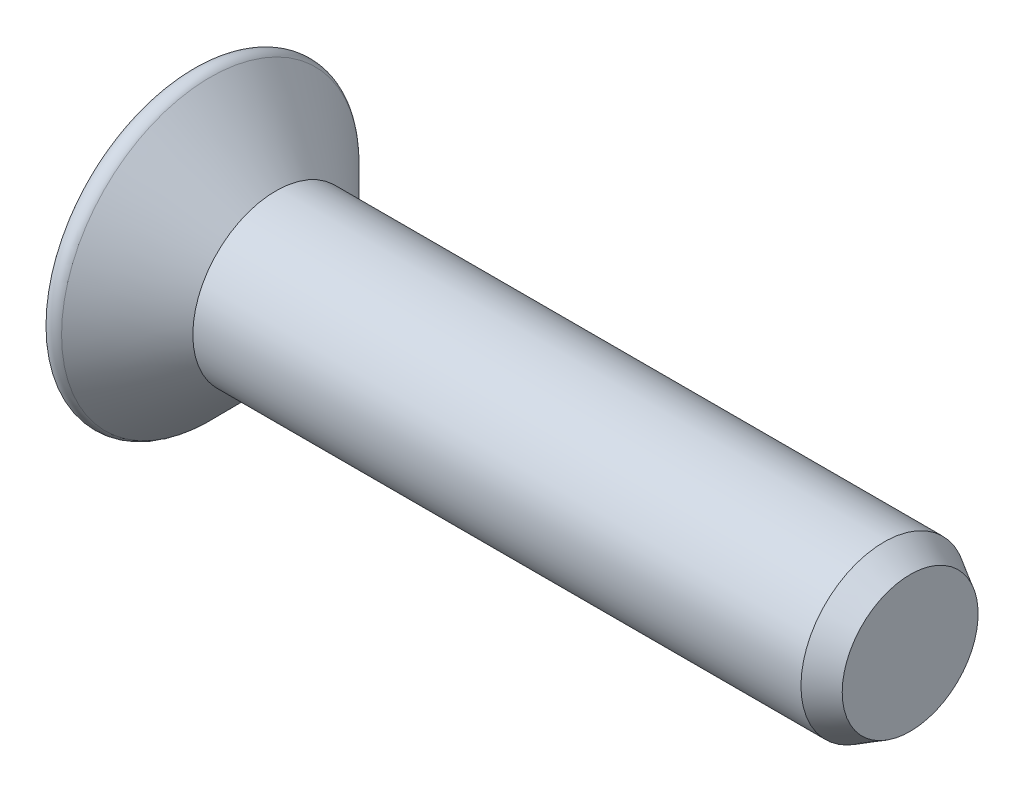
SolidWorks part; units mm, degrees
ref_plane "Front Plane" through (0, 0, 0) normal (0, 0, 1) x (1, 0, 0)
ref_plane "Top Plane" through (0, 0, 0) normal (0, 1, 0) x (1, 0, 0)
ref_plane "Right Plane" through (0, 0, 0) normal (1, 0, 0) x (0, 0, -1)
sketch "Sketch1" plane through (0, 0, 0) normal (0, 0, 1) x (1, 0, 0)
  line L0 (0, 0) -> (6.2784, 0) construction
  line L3 (-1.6, 0) -> (-1.6, -1.8061) construction
  line L4 (-1.6, 0) -> (8.4, 0)
  line L5 (0, 1.1) -> (8.4, 1.1)
  line L6 (8.4, 1.1) -> (8.4, 0)
  line L7 (0, 1.1) -> (-0.869, 1.969)
  arc A0 (-1.1, 1.9365) -> (-1.6, 0) centre (2.4, 0) ccw
  arc A1 (-1.1, 1.9365) -> (-0.869, 1.969) centre (-0.9723, 1.8658) cw
  dimension "D1" = 45
  dimension "l" = 9.5
revolve "Revolve1" add sketch "Sketch1" angle 360 about L0
cosmetic thread "ThreadCosmetic" [suppressed] parameters "D1"=9.3, "D2"=1.65
chamfer "Chamfer1" distance 0.2 angle 60 1 edges at (8.4, 0, 1.1) first distance on face at (8.4, 0, 1.1)
sketch "Sketch5" plane through (0, 0, 0) normal (0, 0, 1) x (1, 0, 0)
  line L0 (0.3703, 0.825) -> (0.2069, 0.825)
  line L1 (0.2069, 0.825) -> (0.0481, 1.1)
  line L2 (0.3703, 0.825) -> (0.529, 1.1)
  line L3 (0.0481, 1.1) -> (0.0481, 1.35)
  line L4 (0.529, 1.1) -> (0.529, 1.35)
  line L5 (0.0481, 1.35) -> (0.529, 1.35)
  line L6 (0.2886, 0.825) -> (0.2886, 0) construction
  line L7 (0, 0) -> (7.3035, 0) construction
  line L9 (0, 1.1) -> (0, -1.1) construction
  line L12 (8.0536, 1.1) -> (0, 1.1) construction
  dimension "D2" = 60
  dimension "D3" = 0.25
  dimension "minordia" = 1.65
  dimension "threadstart" = 0.2886
revolve "ThreadSchematic" [suppressed] cut sketch "Sketch5" angle 360 about L7
pattern_linear "ThdSchPat" [suppressed] count 18 spacing 0.4809 along (1, 0, 0) of bodies 105
sketch "Sketch2" plane through (0, 0, 0) normal (0, 0, 1) x (1, 0, 0)
  line L0 (0, 0) -> (5.7679, 0) construction
  line L1 (8.4, 0) -> (6.4947, 1.1)
  line L2 (8.4, 1.1) -> (8.4, 0) construction
  line L4 (6.4947, 1.1) -> (6.4947, 1.2)
  line L5 (6.4947, 1.2) -> (8.5, 1.2)
  line L6 (8.5, 1.2) -> (8.5, 0)
  line L7 (8.5, 0) -> (8.4, 0)
  point P5 (0, 1.1)
  dimension "D1" = 30
  dimension "D2" = 0.1
  dimension "D3" = 0.1
revolve "EndCone" [suppressed] cut sketch "Sketch2" angle 360 about L0
ref_plane "Plane4" through (-1.6, 0, 0) normal (1, 0, 0) x (0, 0, -1)
sketch "Sketch3" plane through (-1.6, 0, 0) normal (1, 0, 0) x (0, 0, -1)
  line L0 (0, 2.343) -> (0, -2.4842) construction
  line L1 (2.7661, 0) -> (-3.4558, 0) construction
  line L2 (-0.22, 1.1) -> (0.22, 1.1)
  line L3 (0.22, 1.1) -> (0.1467, 0.7333)
  line L4 (0, 0) -> (1.9578, 1.9578) construction
  line L5 (0.1467, 0.7333) -> (0.3614, 0.3614)
  line L6 (0.1467, 0.7333) -> (0, 0) construction
  line L7 (-0.1467, 0.7333) -> (-0.3614, 0.3614)
  line L8 (-0.22, 1.1) -> (-0.1467, 0.7333)
  line L9 (1.1, 0.22) -> (1.1, -0.22)
  line L10 (1.1, -0.22) -> (0.7333, -0.1467)
  line L11 (0.7333, -0.1467) -> (0.3614, -0.3614)
  line L12 (0.7333, 0.1467) -> (0.3614, 0.3614)
  line L13 (1.1, 0.22) -> (0.7333, 0.1467)
  line L14 (0.22, -1.1) -> (-0.22, -1.1)
  line L15 (-0.22, -1.1) -> (-0.1467, -0.7333)
  line L16 (-0.1467, -0.7333) -> (-0.3614, -0.3614)
  line L17 (0.1467, -0.7333) -> (0.3614, -0.3614)
  line L18 (0.22, -1.1) -> (0.1467, -0.7333)
  line L19 (-1.1, -0.22) -> (-1.1, 0.22)
  line L20 (-1.1, 0.22) -> (-0.7333, 0.1467)
  line L21 (-0.7333, 0.1467) -> (-0.3614, 0.3614)
  line L22 (-0.7333, -0.1467) -> (-0.3614, -0.3614)
  line L23 (-1.1, -0.22) -> (-0.7333, -0.1467)
  point P14 (0, 1.1)
  point P23 (1.1, 0)
  point P30 (0, -1.1)
  point P37 (-1.1, 0)
  dimension "D1" = 45
  dimension "D3" = 0.44
  dimension "D4" = 75
  dimension "D5" = 1.4667
  dimension "m" = 2.2
extrude "Cut-Extrude1" cut sketch "Sketch3" along normal blind 0.8 draft 6
sketch "Sketch4" plane through (-1.6, 0, 0) normal (1, 0, 0) x (0, 0, -1)
  line L0 (0, 2.1951) -> (0, -2.1951) construction
  line L1 (2.1996, 0) -> (-2.3835, 0) construction
  line L2 (-0.9723, -0.9723) -> (0.9723, 0.9723) construction
  line L3 (1.1, 0.275) -> (-1.1, 0.275)
  line L4 (1.1, 0.275) -> (1.1, -0.275)
  line L5 (1.1, -0.275) -> (-1.1, -0.275)
  line L6 (-1.1, 0.275) -> (-1.1, -0.275)
  line L7 (0.275, 1.1) -> (-0.275, 1.1)
  line L8 (0.275, 1.1) -> (0.275, -1.1)
  line L9 (0.275, -1.1) -> (-0.275, -1.1)
  line L10 (-0.275, 1.1) -> (-0.275, -1.1)
  line L11 (0.9723, 0.9723) -> (0.4468, 0.275)
  line L12 (0.9723, 0.9723) -> (0.275, 0.4468)
  line L13 (0.275, 0.4468) -> (-0.275, 0.4468) construction
  line L14 (0, 0) -> (-0.9723, 0.9723) construction
  line L15 (-0.9723, -0.9723) -> (-0.275, -0.4468)
  line L16 (-0.9723, -0.9723) -> (-0.4468, -0.275)
  line L17 (-0.275, 0.4468) -> (-0.9723, 0.9723)
  line L18 (-0.9723, 0.9723) -> (-0.4468, 0.275)
  line L19 (-0.4468, -0.275) -> (-0.4468, 0.275) construction
  line L20 (0.4468, -0.275) -> (0.9723, -0.9723)
  line L21 (0.9723, -0.9723) -> (0.275, -0.4468)
  circle A0 centre (0, 0) radius 1.375 construction
  dimension "D1" = 2.75
  dimension "D2" = 0.55
  dimension "m" = 2.2
  dimension "D3" = 45
  dimension "D4" = 8
  dimension "D5" = 45
extrude "TypeZ" [suppressed] cut sketch "Sketch4" along normal blind 0.8
equation "\"D1@ThreadCosmetic\" = \"l@Sketch1\" - \"D1@Chamfer1\""
equation "\"minordia@Sketch5\" = \"D2@ThreadCosmetic\""
equation "\"D1@Plane4\" = \"k@Sketch1\" + \"f@Sketch1\""
equation "\"D5@Sketch3\" = \"m@Sketch3\" * 2 / 3"
equation "\"D3@Sketch3\" = \"m@Sketch3\" / 5"
equation "\"D1@Cut-Extrude1\" =  ( \"k@Sketch1\" + \"f@Sketch1\" )  / 2"
equation "\"D2@Sketch4\" =  \"m@Sketch4\" / 4"
equation "\"D1@TypeZ\" =  ( \"k@Sketch1\" + \"f@Sketch1\" )  / 2"
equation "\"D1@Sketch4\" = \"m@Sketch4\" * 5 / 4"
equation "\"m@Sketch4\" = \"m@Sketch3\""
equation "\"threadstart@Sketch5\" = \"advance@Sketch5\"*0.6"
equation "\"D1@ThdSchPat\" = int(((\"l@Sketch1\"-\"k@Sketch1\")/\"advance@Sketch5\") + 0.999)"
equation "\"D3@ThdSchPat\" = \"advance@Sketch5\""
